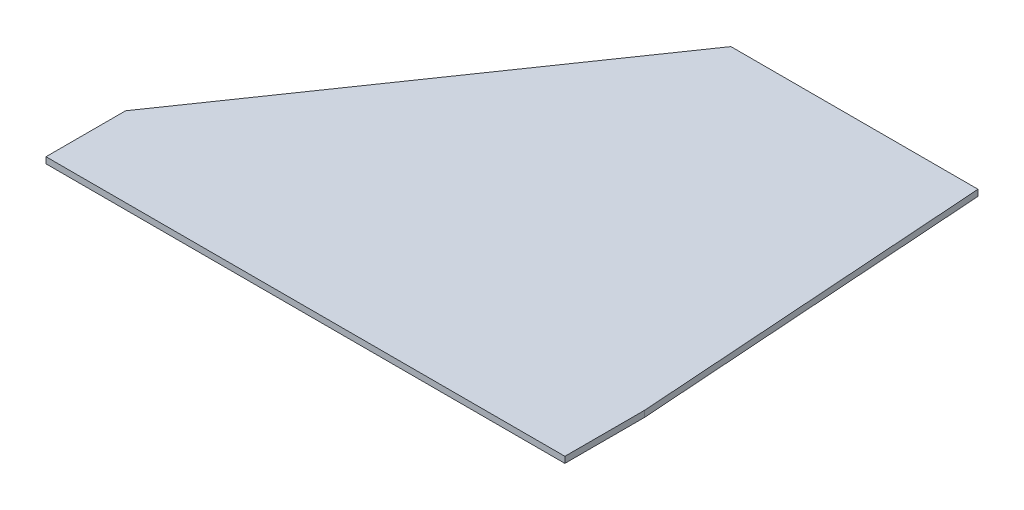
SolidWorks part; units mm, degrees
ref_plane "Front Plane" through (0, 0, 0) normal (0, 0, 1) x (1, 0, 0)
ref_plane "Top Plane" through (0, 0, 0) normal (0, 1, 0) x (1, 0, 0)
ref_plane "Right Plane" through (0, 0, 0) normal (1, 0, 0) x (0, 0, -1)
sketch "Sketch1" plane through (0, 0, 0) normal (0, 1, 0) x (1, 0, 0)
  line L0 (0, 40.894) -> (127, 225.044)
  line L1 (0, 0) -> (266.7, 0)
  line L2 (0, 0) -> (0, 40.894)
  line L3 (0, 40.894) -> (266.7, 40.894)
  line L4 (266.7, 0) -> (266.7, 40.894)
  line L5 (127, 225.044) -> (254, 225.044)
  line L6 (254, 225.044) -> (266.7, 40.894)
  dimension "D1" = 266.7
  dimension "D2" = 127
  dimension "D3" = 184.15
  dimension "D4" = 127
  dimension "D5" = 40.894
extrude "Boss-Extrude1" add sketch "Sketch1" along normal blind 3.175 contours L1 L4 L3 L2 | L6 L5 L0 L3 region at (133.35, 0, -20.447) region at (158.5452, 0, -122.0784)
